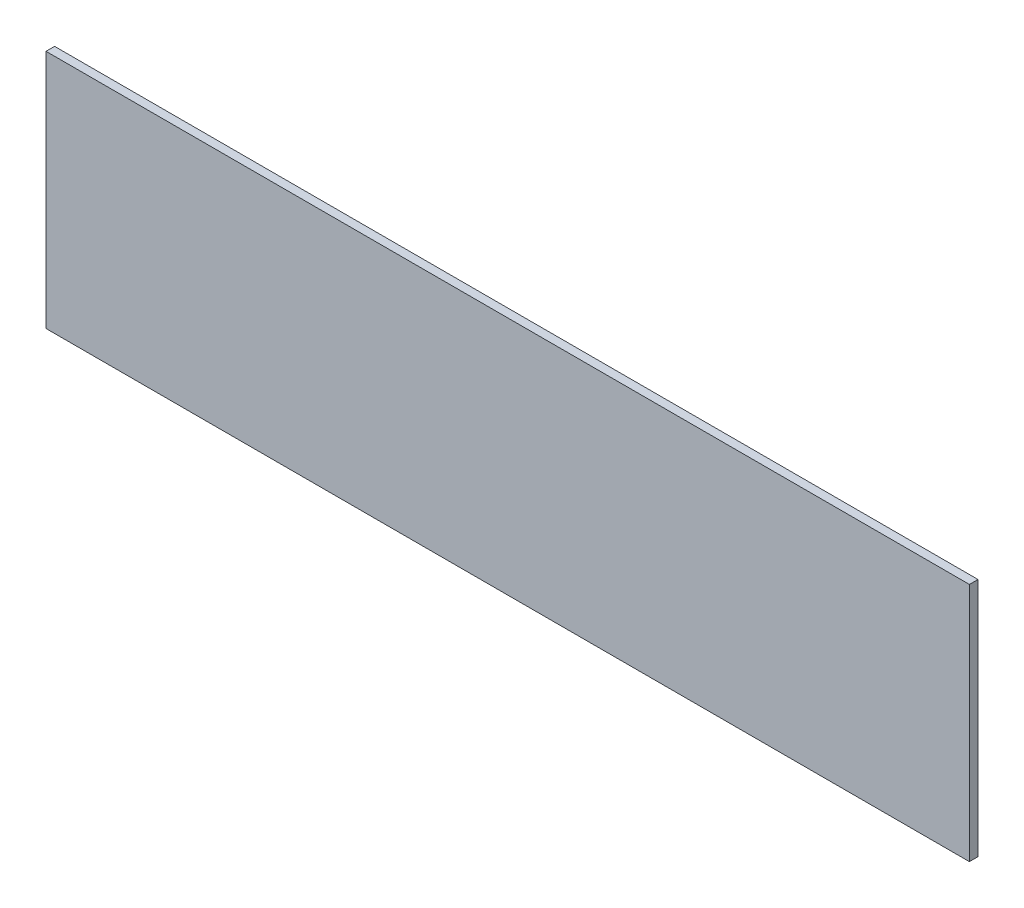
SolidWorks part; units mm, degrees
ref_plane "Front Plane" through (0, 0, 0) normal (0, 0, 1) x (1, 0, 0)
ref_plane "Top Plane" through (0, 0, 0) normal (0, 1, 0) x (1, 0, 0)
ref_plane "Right Plane" through (0, 0, 0) normal (1, 0, 0) x (0, 0, -1)
sketch "Sketch2" plane through (0, 0, 0) normal (0, 0, 1) x (1, 0, 0)
  line L1 (0, 0) -> (-254, 0)
  line L2 (0, 0) -> (0, 66.04)
  line L3 (0, 66.04) -> (-254, 66.04)
  line L4 (-254, 0) -> (-254, 66.04)
  dimension "D1" = 66.04
  dimension "D2" = 254
extrude "Boss-Extrude1" add sketch "Sketch2" along normal blind 2.3622
